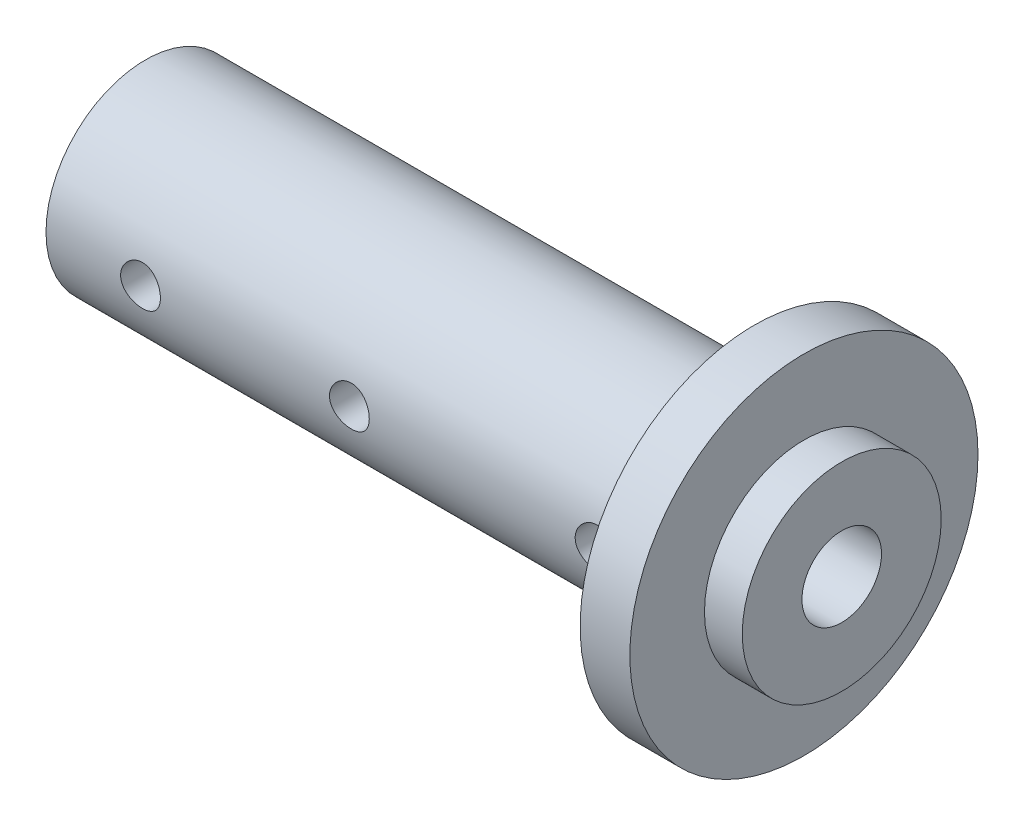
SolidWorks part; units mm, degrees
material "Plain Carbon Steel"
ref_plane "Front Plane" through (0, 0, 0) normal (0, 0, 1) x (1, 0, 0)
ref_plane "Top Plane" through (0, 0, 0) normal (0, 1, 0) x (1, 0, 0)
ref_plane "Right Plane" through (0, 0, 0) normal (1, 0, 0) x (0, 0, -1)
sketch "Sketch1" plane through (0, 0, 0) normal (0, 1, 0) x (1, 0, 0)
  line L1 (-3.8, 17.5) -> (-8.8, 17.5)
  line L2 (-8.8, 17.5) -> (-8.8, 10)
  line L3 (-8.8, 10) -> (-70, 10)
  line L4 (-70, 10) -> (-70, 0)
  line L5 (-70, 0) -> (0, 0) construction
  line L6 (0, 0) -> (-70, 0)
  line L7 (-3.8, 17.5) -> (-3.8, 10)
  line L8 (-3.8, 10) -> (0, 10)
  line L9 (0, 10) -> (0, 4)
  line L10 (0, 4) -> (-19, 4)
  line L11 (-19, 4) -> (-19, 0)
  dimension "D1" = 5
  dimension "D2" = 17.5
  dimension "D3" = 10
  dimension "D4" = 70
  dimension "D5" = 3.8
  dimension "D6" = 4
  dimension "D7" = 19
revolve "Revolve2" add sketch "Sketch1" angle 360 about L6 region at (-36.3027, 0, -5.8407)
ref_plane "Plane2" through (0, 7.0711, 7.0711) normal (0, 0.7071, 0.7071) x (1, 0, 0)
sketch "Sketch5" plane through (0, 0, 0) normal (0, 0, 1) x (1, 0, 0)
  line L0 (-8.8, 17.5) -> (-8.8, -17.5) construction
  circle A0 centre (-39.5, 0) radius 2
  circle A1 centre (-60.5, 0) radius 2
  circle A2 centre (-39.5, 0) radius 2 construction
  circle A3 centre (-60.5, 0) radius 2 construction
  circle A4 centre (-14.8, 0) radius 2
  point P10 (0, 0)
  dimension "D1" = 6
extrude "Cut-Extrude2" cut sketch "Sketch5" against normal through all both and the other way through all
